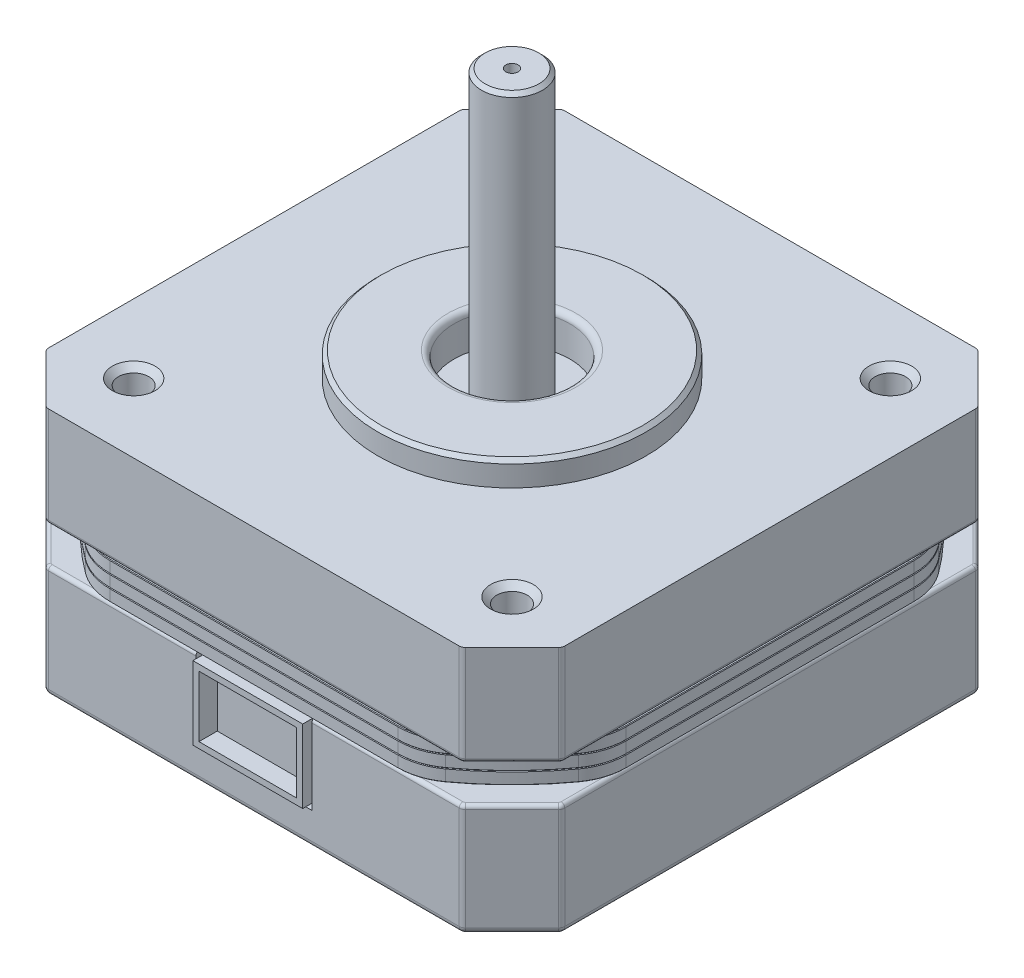
SolidWorks part; units mm, degrees
note: The reader was unsure of these and kept them because the rebuilt part matched: shared geometry of "Эскиз1<3>".
ref_plane "Спереди" through (0, 0, 0) normal (0, 0, 1) x (1, 0, 0)
ref_plane "Сверху" through (0, 0, 0) normal (0, 1, 0) x (1, 0, 0)
ref_plane "Справа" through (0, 0, 0) normal (1, 0, 0) x (0, 0, -1)
sketch "Эскиз1" plane through (0, 0, 0) normal (0, 1, 0) x (1, 0, 0)
  line L0 (-21.15, 17.0338) -> (-17.0338, 21.15)
  line L1 (-21.15, 21.15) -> (21.15, 21.15)
  line L2 (-21.15, 21.15) -> (-21.15, -21.15)
  line L3 (-21.15, -21.15) -> (21.15, -21.15)
  line L4 (21.15, 21.15) -> (21.15, -21.15)
  line L5 (-21.15, 21.15) -> (21.15, -21.15) construction
  line L6 (-21.15, -21.15) -> (21.15, 21.15) construction
  line L7 (-17.0338, 21.15) -> (17.0338, 21.15)
  line L8 (17.0338, 21.15) -> (21.15, 17.0338)
  line L9 (21.15, 17.0338) -> (21.15, -17.0338)
  line L10 (21.15, -17.0338) -> (17.0338, -21.15)
  line L11 (17.0338, -21.15) -> (-17.0338, -21.15)
  line L12 (-17.0338, -21.15) -> (-21.15, -17.0338)
  point P0 (0, 0)
  dimension "D1" = 42.3
  dimension "D2" = 54
extrude "Бобышка-Вытянуть1" add sketch "Эскиз1" along normal blind 9.2 contours L12 L3 L10 L4 L8 L1 L0 L2
extrude "Бобышка-Вытянуть2" add sketch "Эскиз1<3>" against normal blind 8.2 from offset 20.4 separate body contours L12 L3 L10 L4 L8 L1 L0 L2
sketch "Эскиз1<3>" plane through (0, 0, 0) normal (0, 1, 0) x (1, 0, 0) same geometry as "Эскиз1"
sketch "Эскиз2" plane through (0, 9.2, 0) normal (0, 1, 0) x (1, 0, 0)
  line L16 (-21.15, -17.0338) -> (-17.0338, -21.15)
  line L17 (-17.0338, -21.15) -> (17.0338, -21.15)
  line L18 (17.0338, -21.15) -> (21.15, -17.0338)
  line L19 (21.15, -17.0338) -> (21.15, 17.0338)
  line L20 (21.15, 17.0338) -> (17.0338, 21.15)
  line L21 (17.0338, 21.15) -> (-17.0338, 21.15)
  line L22 (-17.0338, 21.15) -> (-21.15, 17.0338)
  line L23 (-21.15, 17.0338) -> (-21.15, -17.0338)
  line L25 (-11.7974, -21.15) -> (11.7974, -21.15)
  line L27 (21.15, -11.7974) -> (21.15, 11.7974)
  line L29 (11.7974, 21.15) -> (-11.7974, 21.15)
  line L31 (-21.15, 11.7974) -> (-21.15, -11.7974)
  arc A0 (-20.1875, -14.7467) -> (-14.7467, -20.1875) centre (0, 0) ccw
  arc A1 (-14.7467, 20.1875) -> (-20.1875, 14.7467) centre (0, 0) ccw
  arc A2 (20.1875, 14.7467) -> (14.7467, 20.1875) centre (0, 0) ccw
  arc A3 (14.7467, -20.1875) -> (20.1875, -14.7467) centre (0, 0) ccw
  arc A4 (14.7467, 20.1875) -> (11.7974, 21.15) centre (11.7974, 16.15) ccw
  arc A5 (21.15, 11.7974) -> (20.1875, 14.7467) centre (16.15, 11.7974) ccw
  arc A6 (20.1875, -14.7467) -> (21.15, -11.7974) centre (16.15, -11.7974) ccw
  arc A7 (11.7974, -21.15) -> (14.7467, -20.1875) centre (11.7974, -16.15) ccw
  arc A8 (-14.7467, -20.1875) -> (-11.7974, -21.15) centre (-11.7974, -16.15) ccw
  arc A9 (-20.1875, -14.7467) -> (-21.15, -11.7974) centre (-16.15, -11.7974) cw
  arc A10 (-20.1875, 14.7467) -> (-21.15, 11.7974) centre (-16.15, 11.7974) ccw
  arc A11 (-11.7974, 21.15) -> (-14.7467, 20.1875) centre (-11.7974, 16.15) ccw
  point P22 (21.15, 13.3296)
  point P27 (13.3296, -21.15)
  point P36 (-13.3296, 21.15)
  dimension "D1" = 50
  dimension "D3" = 5
  dimension "D2" = 0
extrude "Бобышка-Вытянуть3" add sketch "Эскиз2" along normal blind 1 separate body
pattern_linear "Линейный массив1" count 3 spacing 1 along (0, 1, 0) of bodies 105
sketch "Эскиз3" plane through (0, 0, 0) normal (0, -1, 0) x (1, 0, 0)
  circle A0 centre (0, 0) radius 4.75
  dimension "D1" = 9.5
extrude "Вырез-Вытянуть1" cut sketch "Эскиз3" against normal blind 3
sketch "Эскиз4" plane through (0, 3, 0) normal (0, -1, 0) x (1, 0, 0)
  circle A0 centre (0, 0) radius 2.5
  circle A1 centre (0, 0) radius 4.75
  dimension "D1" = 5
extrude "Вырез-Вытянуть2" cut sketch "Эскиз4" against normal blind 0.5
sketch "Эскиз5" plane through (0, 3, 0) normal (0, -1, 0) x (1, 0, 0)
  circle A0 centre (0, 0) radius 0.5
  dimension "D1" = 1
extrude "Вырез-Вытянуть3" cut sketch "Эскиз5" against normal blind 0.5
chamfer "Фаска1" distance 0.3 angle 45 1 edges at (0, 3, -2.5)
fillet "Скругление1" radius 0.5 17 edges at (0, 0, 21.15) (19.0919, 0, 19.0919) (21.15, 0, 0) (19.0919, 0, -19.0919) (0, 0, -21.15) (-19.0919, 0, -19.0919) (-21.15, 0, 0) (-19.0919, 0, 19.0919) (0, 0, -4.75) (21.15, 4.6, 17.0338) (17.0338, 4.6, 21.15) (-17.0338, 4.6, 21.15) (-21.15, 4.6, 17.0338) (-21.15, 4.6, -17.0338) (-17.0338, 4.6, -21.15) (17.0338, 4.6, -21.15) (21.15, 4.6, -17.0338)
fillet "Скругление2" radius 0.5 8 edges at (21.15, 16.3, 17.0338) (17.0338, 16.3, 21.15) (-17.0338, 16.3, 21.15) (-21.15, 16.3, 17.0338) (-21.15, 16.3, -17.0338) (-17.0338, 16.3, -21.15) (17.0338, 16.3, -21.15) (21.15, 16.3, -17.0338)
sketch "Эскиз6" plane through (0, 20.4, 0) normal (0, 1, 0) x (1, 0, 0)
  circle A0 centre (0, 0) radius 11
  circle A1 centre (0, 0) radius 4.75
  dimension "D1" = 22
  dimension "D2" = 9.5
extrude "Бобышка-Вытянуть4" add sketch "Эскиз6" along normal blind 2
sketch "Эскиз7" plane through (0, 20.4, 0) normal (0, 1, 0) x (1, 0, 0)
  circle A2 centre (0, 0) radius 4.75
  circle A3 centre (0, 0) radius 4.75
  dimension "D1" = 0
extrude "Вырез-Вытянуть4" cut sketch "Эскиз7" against normal blind 1
chamfer "Фаска2" distance 0.3 angle 45 1 edges at (0, 22.4, 11)
fillet "Скругление3" radius 0.5 1 edges at (0, 22.4, 4.75)
sketch "Эскиз8" plane through (0, 19.4, 0) normal (0, 1, 0) x (1, 0, 0)
  circle A0 centre (0, 0) radius 2.5
  dimension "D1" = 5
extrude "Бобышка-Вытянуть5" add sketch "Эскиз8" along normal blind 23
chamfer "Фаска4" distance 0.3 angle 45 1 edges at (0, 42.4, 2.5)
sketch "Эскиз9" plane through (0, 42.4, 0) normal (0, 1, 0) x (1, 0, 0)
  circle A0 centre (0, 0) radius 0.5
  dimension "D1" = 1
extrude "Вырез-Вытянуть5" cut sketch "Эскиз9" against normal blind 1
sketch "Эскиз10" plane through (0, 0, 21.15) normal (0, 0, 1) x (1, 0, 0)
  line L0 (0, 0) -> (0, 9.2) construction
  line L1 (-11.7974, 9.2) -> (11.7974, 9.2) construction
  line L2 (-16.8267, 9.2) -> (16.8267, 9.2) construction
  line L3 (-4.75, 2.7) -> (4.75, 2.7)
  line L4 (-4.75, 2.7) -> (-4.75, 9.2)
  line L5 (-4.75, 9.2) -> (4.75, 9.2)
  line L6 (4.75, 2.7) -> (4.75, 9.2)
  line L7 (-4.75, 2.7) -> (4.75, 9.2) construction
  line L8 (-4.75, 9.2) -> (4.75, 2.7) construction
  point P5 (0, 5.95)
  dimension "D1" = 9.5
  dimension "D2" = 6.5
extrude "Вырез-Вытянуть6" cut sketch "Эскиз10" against normal blind 1
sketch "Эскиз11" plane through (0, 0, 20.15) normal (0, 0, 1) x (1, 0, 0)
  line L8 (4.5, 2.95) -> (4.5, 8.95)
  line L9 (4.5, 8.95) -> (-4.5, 8.95)
  line L10 (-4.5, 8.95) -> (-4.5, 2.95)
  line L11 (-4.5, 2.95) -> (4.5, 2.95)
  line L12 (4.5, 2.95) -> (4.5, 8.95)
  line L13 (4.5, 8.95) -> (-4.5, 8.95)
  line L14 (-4.5, 8.95) -> (-4.5, 2.95)
  line L15 (-4.5, 2.95) -> (4.5, 2.95)
  line L20 (4, 3.45) -> (4, 8.45)
  line L21 (4, 8.45) -> (-4, 8.45)
  line L22 (-4, 8.45) -> (-4, 3.45)
  line L23 (-4, 3.45) -> (4, 3.45)
  line L24 (4, 3.45) -> (4, 8.45)
  line L25 (4, 8.45) -> (-4, 8.45)
  line L26 (-4, 8.45) -> (-4, 3.45)
  line L27 (-4, 3.45) -> (4, 3.45)
  dimension "D1" = 0.25
  dimension "D2" = 0.75
extrude "Бобышка-Вытянуть6" add sketch "Эскиз11" along normal blind 1.5 separate body
sketch "Эскиз12" plane through (0, 0, 20.15) normal (0, 0, 1) x (1, 0, 0)
  line L0 (-4, 5.95) -> (4, 5.95) construction
  line L1 (-4, 8.45) -> (-4, 3.45) construction
  line L2 (4, 3.45) -> (4, 8.45) construction
  line L3 (-2.625, 5.95) -> (-2.625, 4.3362) construction
  line L4 (-2.625, 4.3362) -> (-0.875, 4.3362) construction
  line L5 (-0.875, 4.3362) -> (-0.875, 5.95) construction
  line L6 (-0.875, 5.95) -> (-0.875, 4.3362) construction
  line L7 (-0.875, 4.3362) -> (0.875, 4.3362) construction
  line L8 (0.875, 4.3362) -> (0.875, 5.95) construction
  line L9 (0.875, 5.95) -> (0.875, 4.3362) construction
  line L10 (0.875, 4.3362) -> (2.625, 4.3362) construction
  line L11 (2.625, 4.3362) -> (2.625, 5.95) construction
  line L12 (0, 5.95) -> (0, 4.3362) construction
  circle A0 centre (-2.625, 5.95) radius 0.6
  circle A1 centre (-0.875, 5.95) radius 0.6
  circle A2 centre (0.875, 5.95) radius 0.6
  circle A3 centre (2.625, 5.95) radius 0.6
  circle A4 centre (-2.625, 5.95) radius 0.25
  circle A5 centre (-0.875, 5.95) radius 0.25
  circle A6 centre (0.875, 5.95) radius 0.25
  circle A7 centre (2.625, 5.95) radius 0.25
  dimension "D1" = 1.2
  dimension "D2" = 0.5
  dimension "D3" = 1.75
chamfer "Фаска32" distance 0.05 angle 45 32 edges at (-17.6777, 12.2, -17.6777) (-20.9033, 12.2, -13.3486) (-13.3486, 12.2, -20.9033) (-21.15, 12.2, 0) (0, 12.2, -21.15) (-20.9033, 12.2, 13.3486) (13.3486, 12.2, -20.9033) (-17.6777, 12.2, 17.6777) (17.6777, 12.2, -17.6777) (-13.3486, 12.2, 20.9033) (20.9033, 12.2, -13.3486) (0, 12.2, 21.15) (21.15, 12.2, 0) (13.3486, 12.2, 20.9033) (20.9033, 12.2, 13.3486) (17.6777, 12.2, 17.6777) (-17.6777, 11.2, -17.6777) (-20.9033, 11.2, -13.3486) (-13.3486, 11.2, -20.9033) (-21.15, 11.2, 0) (0, 11.2, -21.15) (-20.9033, 11.2, 13.3486) (13.3486, 11.2, -20.9033) (-17.6777, 11.2, 17.6777) (17.6777, 11.2, -17.6777) (-13.3486, 11.2, 20.9033) (20.9033, 11.2, -13.3486) (0, 11.2, 21.15) (21.15, 11.2, 0) (13.3486, 11.2, 20.9033) (20.9033, 11.2, 13.3486) (17.6777, 11.2, 17.6777)
chamfer "Фаска33" distance 0.05 angle 45 32 edges at (-17.6777, 11.2, -17.6777) (-20.9033, 11.2, -13.3486) (-13.3486, 11.2, -20.9033) (-21.15, 11.2, 0) (0, 11.2, -21.15) (-20.9033, 11.2, 13.3486) (13.3486, 11.2, -20.9033) (-17.6777, 11.2, 17.6777) (17.6777, 11.2, -17.6777) (-13.3486, 11.2, 20.9033) (20.9033, 11.2, -13.3486) (0, 11.2, 21.15) (21.15, 11.2, 0) (13.3486, 11.2, 20.9033) (20.9033, 11.2, 13.3486) (17.6777, 11.2, 17.6777) (-17.6777, 10.2, -17.6777) (-20.9033, 10.2, -13.3486) (-13.3486, 10.2, -20.9033) (-21.15, 10.2, 0) (0, 10.2, -21.15) (-20.9033, 10.2, 13.3486) (13.3486, 10.2, -20.9033) (-17.6777, 10.2, 17.6777) (17.6777, 10.2, -17.6777) (-13.3486, 10.2, 20.9033) (20.9033, 10.2, -13.3486) (0, 10.2, 21.15) (21.15, 10.2, 0) (13.3486, 10.2, 20.9033) (20.9033, 10.2, 13.3486) (17.6777, 10.2, 17.6777)
chamfer "Фаска34" distance 0.05 angle 45 32 edges at (-17.6777, 10.2, -17.6777) (-20.9033, 10.2, -13.3486) (-13.3486, 10.2, -20.9033) (-21.15, 10.2, 0) (0, 10.2, -21.15) (-20.9033, 10.2, 13.3486) (13.3486, 10.2, -20.9033) (-17.6777, 10.2, 17.6777) (17.6777, 10.2, -17.6777) (-13.3486, 10.2, 20.9033) (20.9033, 10.2, -13.3486) (0, 10.2, 21.15) (21.15, 10.2, 0) (13.3486, 10.2, 20.9033) (20.9033, 10.2, 13.3486) (17.6777, 10.2, 17.6777) (-17.6777, 9.2, -17.6777) (-20.9033, 9.2, -13.3486) (-13.3486, 9.2, -20.9033) (-21.15, 9.2, 0) (0, 9.2, -21.15) (-20.9033, 9.2, 13.3486) (13.3486, 9.2, -20.9033) (-17.6777, 9.2, 17.6777) (17.6777, 9.2, -17.6777) (-13.3486, 9.2, 20.9033) (20.9033, 9.2, -13.3486) (0, 9.2, 21.15) (21.15, 9.2, 0) (13.3486, 9.2, 20.9033) (20.9033, 9.2, 13.3486) (17.6777, 9.2, 17.6777)
sketch "Эскиз16" plane through (0, 20.4, 0) normal (0, 1, 0) x (1, 0, 0)
  line L1 (-15.5, 15.5) -> (15.5, 15.5) construction
  line L2 (-15.5, 15.5) -> (-15.5, -15.5) construction
  line L3 (-15.5, -15.5) -> (15.5, -15.5) construction
  line L4 (15.5, 15.5) -> (15.5, -15.5) construction
  line L5 (-15.5, 15.5) -> (15.5, -15.5) construction
  line L6 (-15.5, -15.5) -> (15.5, 15.5) construction
  circle A0 centre (-15.5, 15.5) radius 1.25
  circle A1 centre (15.5, 15.5) radius 1.25
  circle A2 centre (15.5, -15.5) radius 1.25
  circle A3 centre (-15.5, -15.5) radius 1.25
  point P0 (0, 0)
  dimension "D1" = 2.5
  dimension "D2" = 31
extrude "Вырез-Вытянуть9" cut sketch "Эскиз16" against normal blind 7
chamfer "Фаска35" distance 0.5 angle 45 4 edges at (-15.5, 20.4, 16.75) (15.5, 20.4, 16.75) (15.5, 20.4, -14.25) (-15.5, 20.4, -14.25)
fillet "Скругление4" radius 0.3 17 edges at (-10.7883, 9.2, 21.15) (-17.018, 9.2, 21.1119) (-19.0919, 9.2, 19.0919) (-21.1119, 9.2, 17.018) (-21.15, 9.2, 0) (-21.1119, 9.2, -17.018) (-19.0919, 9.2, -19.0919) (-17.018, 9.2, -21.1119) (0, 9.2, -21.15) (17.018, 9.2, -21.1119) (19.0919, 9.2, -19.0919) (21.1119, 9.2, -17.018) (21.15, 9.2, 0) (21.1119, 9.2, 17.018) (10.7883, 9.2, 21.15) (17.018, 9.2, 21.1119) (19.0919, 9.2, 19.0919)
fillet "Скругление5" radius 0.3 16 edges at (21.1119, 12.2, 17.018) (21.15, 12.2, 0) (21.1119, 12.2, -17.018) (19.0919, 12.2, -19.0919) (17.018, 12.2, -21.1119) (0, 12.2, -21.15) (-17.018, 12.2, -21.1119) (-19.0919, 12.2, -19.0919) (-21.1119, 12.2, -17.018) (-21.15, 12.2, 0) (-21.1119, 12.2, 17.018) (-19.0919, 12.2, 19.0919) (-17.018, 12.2, 21.1119) (0, 12.2, 21.15) (17.018, 12.2, 21.1119) (19.0919, 12.2, 19.0919)
